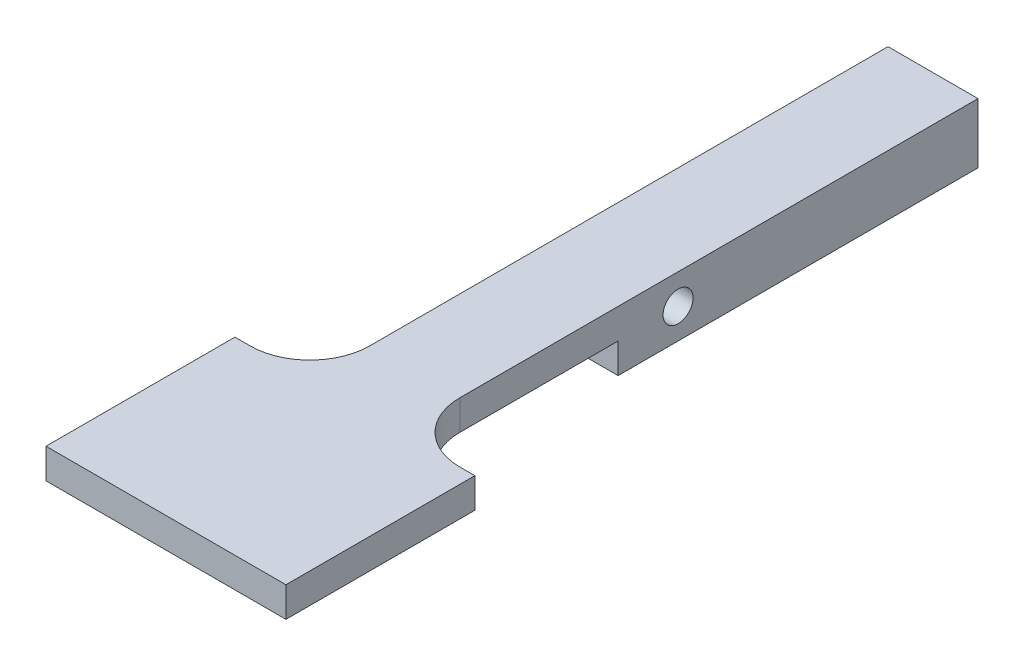
SolidWorks part; units mm, degrees
material "6061 Alloy"
ref_plane "Front Plane" through (0, 0, 0) normal (0, 0, 1) x (1, 0, 0)
ref_plane "Top Plane" through (0, 0, 0) normal (0, 1, 0) x (1, 0, 0)
ref_plane "Right Plane" through (0, 0, 0) normal (1, 0, 0) x (0, 0, -1)
sketch "Sketch1" plane through (0, 0, 0) normal (1, 0, 0) x (0, 0, -1)
  line L0 (0, 1.5875) -> (0, -1.5875)
  line L5 (-76.2, 1.5875) -> (0, 1.5875)
  line L6 (-38.1, -1.5875) -> (-76.2, -1.5875)
  line L8 (-38.1, -1.5875) -> (-38.1, -4.7625)
  line L9 (-38.1, -4.7625) -> (-25.4, -4.7625)
  line L11 (-76.2, 1.5875) -> (-76.2, -1.5875)
  line L12 (-25.4, -4.7625) -> (0, -4.7625)
  line L13 (0, -4.7625) -> (0, -1.5875)
  circle A0 centre (-31.75, -1.5875) radius 1.5875
  point P14 (-31.75, -4.7625)
  dimension "D6" = 3.175
  dimension "D1" = 3.175
  dimension "D4" = 76.2
  dimension "D5" = 3.175
  dimension "D7" = 12.7
  dimension "D8" = 38.1
extrude "Boss-Extrude1" add sketch "Sketch1" along normal blind 9.525 contours L5 | L0 L5 L6 L8 L9 A0 region at (0, 0, 0.7646)
ref_plane "Center Plane" through (4.7625, 0, 0) normal (1, 0, 0) x (0, 0, -1)
sketch "Sketch3" plane through (4.7625, 0, 0) normal (1, 0, 0) x (0, 0, -1)
  line L2 (-76.2, -1.5875) -> (-61.2, -1.5875)
  line L4 (-61.2, -1.5875) -> (-61.2, 1.5875)
  line L5 (-76.2, 1.5875) -> (0, 1.5875) construction
  line L6 (-61.2, 1.5875) -> (-76.2, 1.5875)
  line L7 (-76.2, 1.5875) -> (-76.2, -1.5875)
  line L9 (-76.2, 1.5875) -> (-81.2, 1.5875)
  line L10 (-76.2, 1.5875) -> (-76.2, -1.5875)
  line L11 (-76.2, -1.5875) -> (-81.2, -1.5875)
  line L12 (-81.2, 1.5875) -> (-81.2, -1.5875)
  line L13 (-76.2, 1.5875) -> (-76.2, -1.5875) construction
  line L14 (-38.1, -1.5875) -> (-76.2, -1.5875) construction
  dimension "D1" = 15
  dimension "D2" = 20
extrude "Boss-Extrude2" add sketch "Sketch3" along normal mid plane 25.4 contours L6 L7 L2 L4 | L9 L12 L11 L7 region at (4.7625, 0, 68.7) region at (4.7625, 0, 78.7)
fillet "Fillet1" radius 6.35 2 edges at (0, 0, 61.2) (9.525, 0, 61.2)
